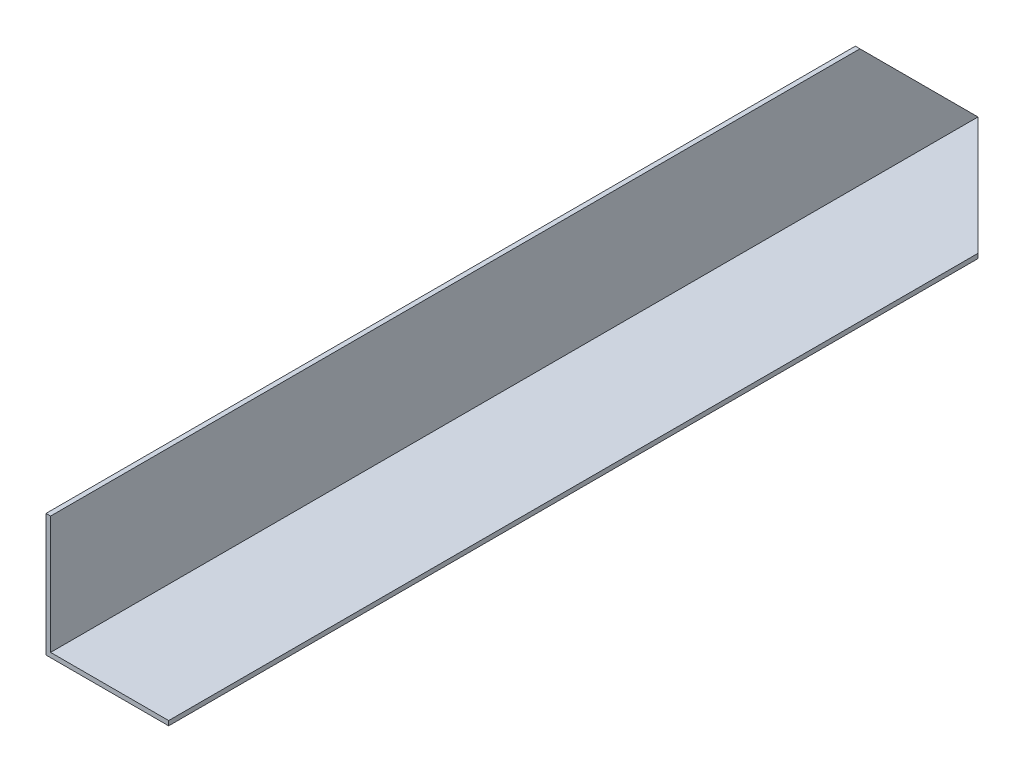
SolidWorks part; units mm, degrees
material "1060 Legierung"
ref_plane "Ebene vorne" through (0, 0, 0) normal (0, 0, 1) x (1, 0, 0)
ref_plane "Ebene oben" through (0, 0, 0) normal (0, 1, 0) x (1, 0, 0)
ref_plane "Ebene rechts" through (0, 0, 0) normal (1, 0, 0) x (0, 0, -1)
sketch "Skizze1" plane through (0, 0, 300) normal (0, 0, -1) x (-1, 0, 0)
  line L0 (461.5, -500) -> (500, -500)
  line L1 (-500, -500) -> (500, -500) construction
  line L2 (500, -500) -> (500, -461.5)
  line L3 (500, -500) -> (500, 500) construction
  line L4 (500, -461.5) -> (501.5, -461.5)
  line L5 (501.5, -461.5) -> (501.5, -501.5)
  line L6 (501.5, -501.5) -> (461.5, -501.5)
  line L7 (461.5, -501.5) -> (461.5, -500)
  dimension "D1" = 40
  dimension "D2" = 1.5
extrude "Aufsatz-Linear austragen1" add sketch "Skizze1" along normal offset from surface (303.9 mm away) 0.1
sketch "Skizze2" plane through (0, -501.5, 0) normal (0, -1, 0) x (1, 0, 0)
  line L0 (-461.5, -3.9) -> (-501.5, -3.9)
  line L1 (-501.5, -3.9) -> (-461.5, 36.1)
  line L2 (-461.5, -3.9) -> (-461.5, 300) construction
  line L3 (-461.5, 36.1) -> (-461.5, -3.9)
  dimension "D1" = 45
extrude "Schnitt-Linear austragen1" cut sketch "Skizze2" against normal up to surface (1.5 mm away) up to face at (-480.75, -500, 148.05)
sketch "Skizze3" plane through (-501.5, 0, 0) normal (-1, 0, 0) x (0, 0, 1)
  line L2 (-3.9, -461.5) -> (300, -461.5) construction
  line L3 (-3.9, -461.5) -> (-3.9, -501.5)
  line L4 (-3.9, -461.5) -> (36.1, -461.5)
  line L5 (36.1, -461.5) -> (-3.9, -501.5)
  dimension "D1" = 45
extrude "Schnitt-Linear austragen2" cut sketch "Skizze3" against normal up to surface (1.5 mm away) up to face at (-500, -484.6, 117.96)
